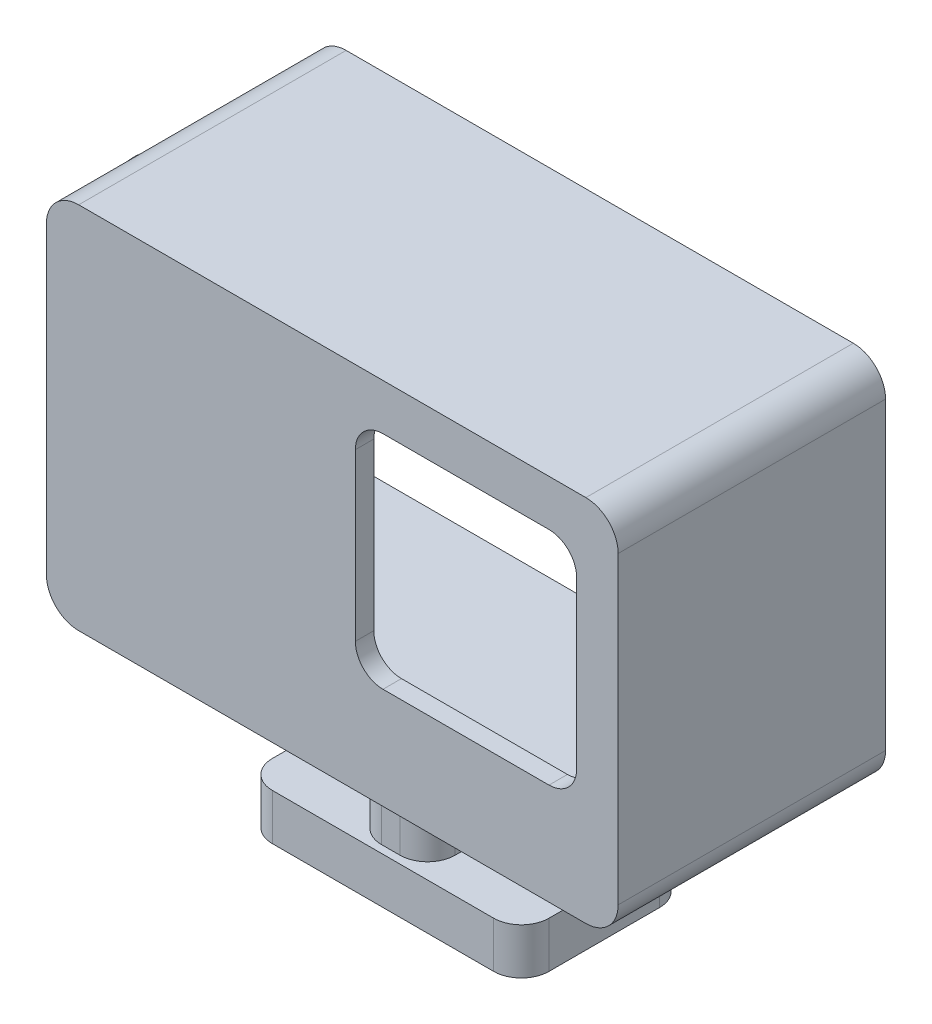
SolidWorks part; units mm, degrees
ref_plane "Front Plane" through (0, 0, 0) normal (0, 0, 1) x (1, 0, 0)
ref_plane "Top Plane" through (0, 0, 0) normal (0, 1, 0) x (1, 0, 0)
ref_plane "Right Plane" through (0, 0, 0) normal (1, 0, 0) x (0, 0, -1)
sketch "Sketch1" plane through (0, 0, 0) normal (0, 0, 1) x (1, 0, 0)
  line L4 (29.5, 80) -> (29.5, 47)
  line L5 (27.5, 45) -> (-27.5, 45)
  line L6 (-29.5, 47) -> (-29.5, 80)
  line L7 (-27.5, 82) -> (27.5, 82)
  line L8 (31, 80) -> (31, 47)
  line L9 (27.5, 43.5) -> (-27.5, 43.5)
  line L10 (-31, 47) -> (-31, 80)
  line L11 (-27.5, 83.5) -> (27.5, 83.5)
  arc A4 (29.5, 80) -> (27.5, 82) centre (27.5, 80) ccw
  arc A5 (27.5, 45) -> (29.5, 47) centre (27.5, 47) ccw
  arc A6 (-29.5, 47) -> (-27.5, 45) centre (-27.5, 47) ccw
  arc A7 (-27.5, 82) -> (-29.5, 80) centre (-27.5, 80) ccw
  arc A8 (27.5, 43.5) -> (31, 47) centre (27.5, 47) ccw
  arc A9 (-31, 47) -> (-27.5, 43.5) centre (-27.5, 47) ccw
  arc A10 (-27.5, 83.5) -> (-31, 80) centre (-27.5, 80) ccw
  arc A11 (31, 80) -> (27.5, 83.5) centre (27.5, 80) ccw
  dimension "D1" = 1.5
extrude "Boss-Extrude1" add sketch "Sketch1" against normal blind 27
sketch "Sketch2" plane through (0, 0, 0) normal (0, 0, 1) x (1, 0, 0)
  line L4 (27.5, 83.5) -> (-27.5, 83.5)
  line L5 (-31, 80) -> (-31, 47)
  line L6 (-27.5, 43.5) -> (27.5, 43.5)
  line L7 (31, 47) -> (31, 80)
  line L8 (27.5, 83.5) -> (-27.5, 83.5)
  line L9 (-31, 80) -> (-31, 47)
  line L10 (-27.5, 43.5) -> (27.5, 43.5)
  line L11 (31, 47) -> (31, 80)
  line L33 (23.5, 78.5) -> (5.5, 78.5)
  line L34 (2.5, 75.5) -> (2.5, 57.5)
  line L35 (5.5, 54.5) -> (23.5, 54.5)
  line L36 (26.5, 57.5) -> (26.5, 75.5)
  line L37 (23.5, 78.5) -> (5.5, 78.5)
  line L38 (2.5, 75.5) -> (2.5, 57.5)
  line L39 (5.5, 54.5) -> (23.5, 54.5)
  line L40 (26.5, 57.5) -> (26.5, 75.5)
  arc A4 (31, 80) -> (27.5, 83.5) centre (27.5, 80) ccw
  arc A5 (-27.5, 83.5) -> (-31, 80) centre (-27.5, 80) ccw
  arc A6 (-31, 47) -> (-27.5, 43.5) centre (-27.5, 47) ccw
  arc A7 (27.5, 43.5) -> (31, 47) centre (27.5, 47) ccw
  arc A8 (31, 80) -> (27.5, 83.5) centre (27.5, 80) ccw
  arc A9 (-27.5, 83.5) -> (-31, 80) centre (-27.5, 80) ccw
  arc A10 (-31, 47) -> (-27.5, 43.5) centre (-27.5, 47) ccw
  arc A11 (27.5, 43.5) -> (31, 47) centre (27.5, 47) ccw
  arc A36 (26.5, 75.5) -> (23.5, 78.5) centre (23.5, 75.5) ccw
  arc A37 (5.5, 78.5) -> (2.5, 75.5) centre (5.5, 75.5) ccw
  arc A38 (2.5, 57.5) -> (5.5, 54.5) centre (5.5, 57.5) ccw
  arc A39 (23.5, 54.5) -> (26.5, 57.5) centre (23.5, 57.5) ccw
  arc A40 (26.5, 75.5) -> (23.5, 78.5) centre (23.5, 75.5) ccw
  arc A41 (5.5, 78.5) -> (2.5, 75.5) centre (5.5, 75.5) ccw
  arc A42 (2.5, 57.5) -> (5.5, 54.5) centre (5.5, 57.5) ccw
  arc A43 (23.5, 54.5) -> (26.5, 57.5) centre (23.5, 57.5) ccw
  dimension "D1" = 0
  dimension "D2" = 0
extrude "Boss-Extrude2" add sketch "Sketch2" along normal blind 2
sketch "Sketch3" plane through (0, 43.5, 0) normal (0, -1, 0) x (1, 0, 0)
  line L0 (0, -26.7959) -> (0, 2.1312) construction
  line L1 (0, -12.5) -> (0, -149.9931) construction
  line L2 (0, 223.5) -> (0, -9.5) construction
  line L3 (-19.3813, 2.1312) -> (-19.3813, -26.7959) construction
  line L4 (-4, -4.3323) -> (4, -4.3323)
  line L5 (-4, -4.3323) -> (-4, -20.3323)
  line L6 (-4, -20.3323) -> (4, -20.3323)
  line L7 (4, -4.3323) -> (4, -20.3323)
  line L8 (-19.3813, -12.3323) -> (31.0779, -12.3323) construction
  dimension "D1" = 4
  dimension "D2" = 8
  dimension "D3" = 16
  dimension "D4" = 8
extrude "Boss-Extrude3" add sketch "Sketch3" along normal blind 10
sketch "Sketch4" plane through (0, 33.5, 0) normal (0, -1, 0) x (1, 0, 0)
  line L0 (0, 0) -> (0, -30.0787) construction
  line L1 (-15, -3.5) -> (15, -3.5)
  line L2 (-15, -3.5) -> (-15, -21.5)
  line L3 (-15, -21.5) -> (15, -21.5)
  line L4 (15, -3.5) -> (15, -21.5)
  line L5 (0, -12.5) -> (0, -149.9931) construction
  line L6 (58.9956, -12.5) -> (0, -12.5) construction
  point P9 (0, 0)
  dimension "D1" = 15
  dimension "D2" = 30
  dimension "D3" = 18
  dimension "D4" = 9
extrude "Boss-Extrude4" add sketch "Sketch4" along normal blind 5
fillet "Fillet1" radius 3 4 edges at (-15, 31, -21.5) (15, 31, -21.5) (-15, 31, -3.5) (15, 31, -3.5)
fillet "Fillet2" radius 3 4 edges at (4, 38.5, -4.3323) (-4, 38.5, -4.3323) (-4, 38.5, -20.3323) (4, 38.5, -20.3323)
sketch "Sketch5" plane through (-4, 0, 0) normal (-1, 0, 0) x (0, 0, 1)
  line L0 (-12.5, 43.5) -> (-12.5, 33.5) construction
  line L1 (-27, 43.5) -> (2, 43.5) construction
  line L2 (-6.5, 33.5) -> (-18.5, 33.5) construction
  circle A0 centre (-12.5, 38.5) radius 3
extrude "Boss-Extrude5" add sketch "Sketch5" along normal blind 32
sketch "Sketch6" plane through (-36, 0, 0) normal (-1, 0, 0) x (0, 0, 1)
  circle A0 centre (-12.5, 38.5) radius 4.5
extrude "Boss-Extrude6" add sketch "Sketch6" along normal blind 5
sketch "Sketch7" plane through (-31, 0, 0) normal (-1, 0, 0) x (0, 0, 1)
  line L0 (-12.5, 83.5) -> (-12.5, 43.5) construction
  line L1 (-27, 83.5) -> (2, 83.5) construction
  line L2 (-27, 43.5) -> (2, 43.5) construction
  circle A0 centre (-12.5, 71.5) radius 5
  circle A1 centre (-12.5, 56.5) radius 5
  dimension "D1" = 12
  dimension "D2" = 15
extrude "Boss-Extrude7" add sketch "Sketch7" along normal blind 5
